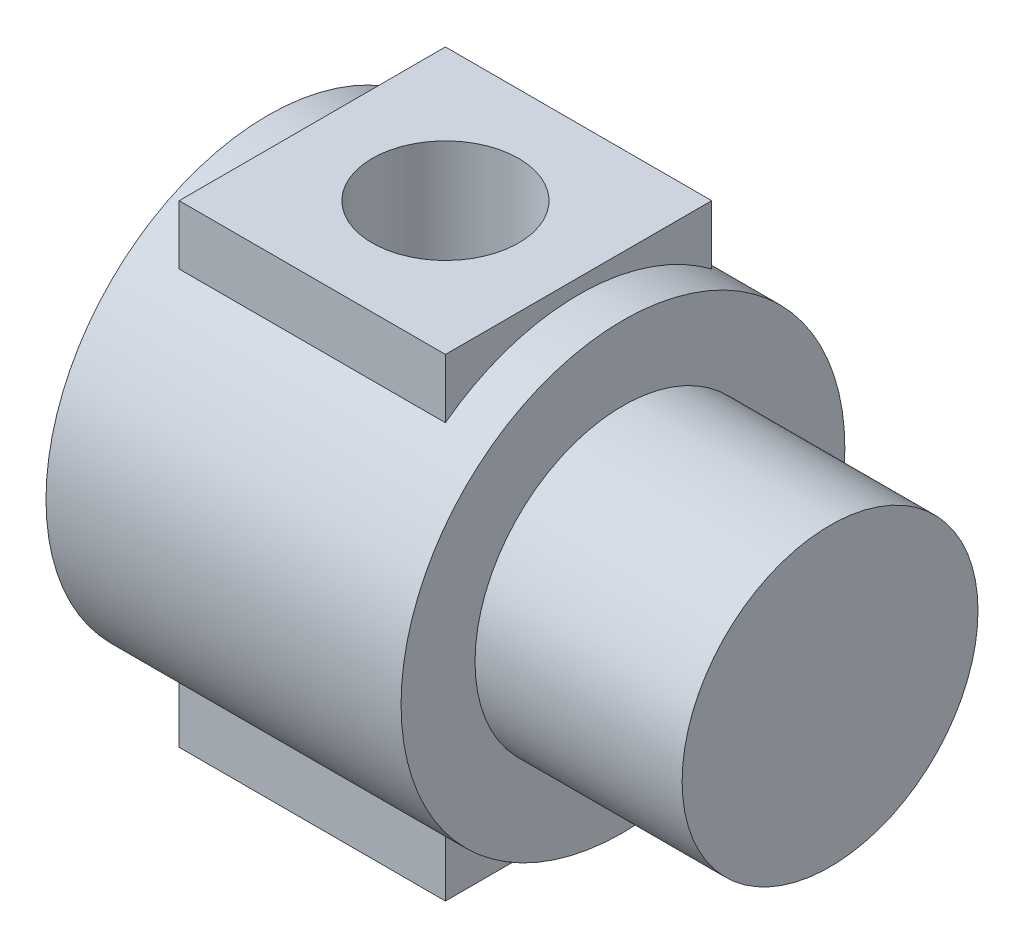
SolidWorks part; units mm, degrees
ref_plane "Front Plane" through (0, 0, 0) normal (0, 0, 1) x (1, 0, 0)
ref_plane "Top Plane" through (0, 0, 0) normal (0, 1, 0) x (1, 0, 0)
ref_plane "Right Plane" through (0, 0, 0) normal (1, 0, 0) x (0, 0, -1)
sketch "Reg_Outlet_Adapter Sketch" plane through (0, 0, 0) normal (0, 0, 1) x (1, 0, 0)
  line L0 (-1000, 0) -> (1000, 0) construction
  line L1 (14, 0) -> (14, 10)
  line L2 (14, 10) -> (0, 10)
  line L3 (0, 10) -> (0, 15)
  line L4 (0, 15) -> (-24, 15)
  line L5 (-24, 15) -> (-24, 0)
  line L6 (-24, 0) -> (14, 0)
revolve "Reg_Outlet_Adapter" add sketch "Reg_Outlet_Adapter Sketch" angle 360 about L0
ref_axis "Engine Axis" through (15.9, 0, 0) along (-1, 0, 0)
sketch "Side Boss Sketch" plane through (0, 0, 0) normal (0, 0, 1) x (1, 0, 0)
  line L0 (-21, 0) -> (-3, 0)
  line L1 (-3, 0) -> (-3, 16)
  line L2 (-3, 16) -> (-21, 16)
  line L3 (-21, 16) -> (-21, 0)
extrude "Side Boss" add sketch "Side Boss Sketch" along normal mid plane 18
sketch "Side Boss 2 Sketch" plane through (0, 0, 0) normal (0, 0, 1) x (1, 0, 0)
  line L0 (-21, -16) -> (-3, -16)
  line L1 (-3, -16) -> (-3, 0)
  line L2 (-3, 0) -> (-21, 0)
  line L3 (-21, 0) -> (-21, -16)
extrude "Side Boss 2" add sketch "Side Boss 2 Sketch" along normal mid plane 18
sketch "Bottom Port Sketch" plane through (0, 0, 0) normal (0, 0, 1) x (1, 0, 0)
  line L0 (-1000, 0) -> (1000, 0) construction
  line L1 (-25, 0) -> (-25, 4.953)
  line L2 (-25, 4.953) -> (-13.5, 4.953)
  line L3 (-13.5, 4.953) -> (-13.5, 0)
  line L4 (-13.5, 0) -> (-25, 0)
revolve "Bottom Port" cut sketch "Bottom Port Sketch" angle 360 about L0
sketch "Side Port Sketch" plane through (0, 0, 0) normal (0, 0, 1) x (1, 0, 0)
  line L0 (-12, -60) -> (-12, 60) construction
  line L1 (-12, 5.5) -> (-7.047, 5.5)
  line L2 (-7.047, 5.5) -> (-7.047, 17)
  line L3 (-7.047, 17) -> (-12, 17)
  line L4 (-12, 17) -> (-12, 5.5)
revolve "Side Port" cut sketch "Side Port Sketch" angle 360 about L0
sketch "Side Passage Sketch" plane through (0, 0, 0) normal (0, 0, 1) x (1, 0, 0)
  line L0 (-12, -60) -> (-12, 60) construction
  line L1 (-12, 0) -> (-10, 0)
  line L2 (-10, 0) -> (-10, 5.5)
  line L3 (-10, 5.5) -> (-12, 5.5)
  line L4 (-12, 5.5) -> (-12, 0)
revolve "Side Passage" cut sketch "Side Passage Sketch" angle 360 about L0
sketch "Side Port 2 Sketch" plane through (0, 0, 0) normal (0, 0, 1) x (1, 0, 0)
  line L0 (-12, -60) -> (-12, 60) construction
  line L1 (-12, -17) -> (-7.047, -17)
  line L2 (-7.047, -17) -> (-7.047, -5.5)
  line L3 (-7.047, -5.5) -> (-12, -5.5)
  line L4 (-12, -5.5) -> (-12, -17)
revolve "Side Port 2" cut sketch "Side Port 2 Sketch" angle 360 about L0
sketch "Side Passage 2 Sketch" plane through (0, 0, 0) normal (0, 0, 1) x (1, 0, 0)
  line L0 (-12, -60) -> (-12, 60) construction
  line L1 (-12, -5.5) -> (-10, -5.5)
  line L2 (-10, -5.5) -> (-10, 0)
  line L3 (-10, 0) -> (-12, 0)
  line L4 (-12, 0) -> (-12, -5.5)
revolve "Side Passage 2" cut sketch "Side Passage 2 Sketch" angle 360 about L0
